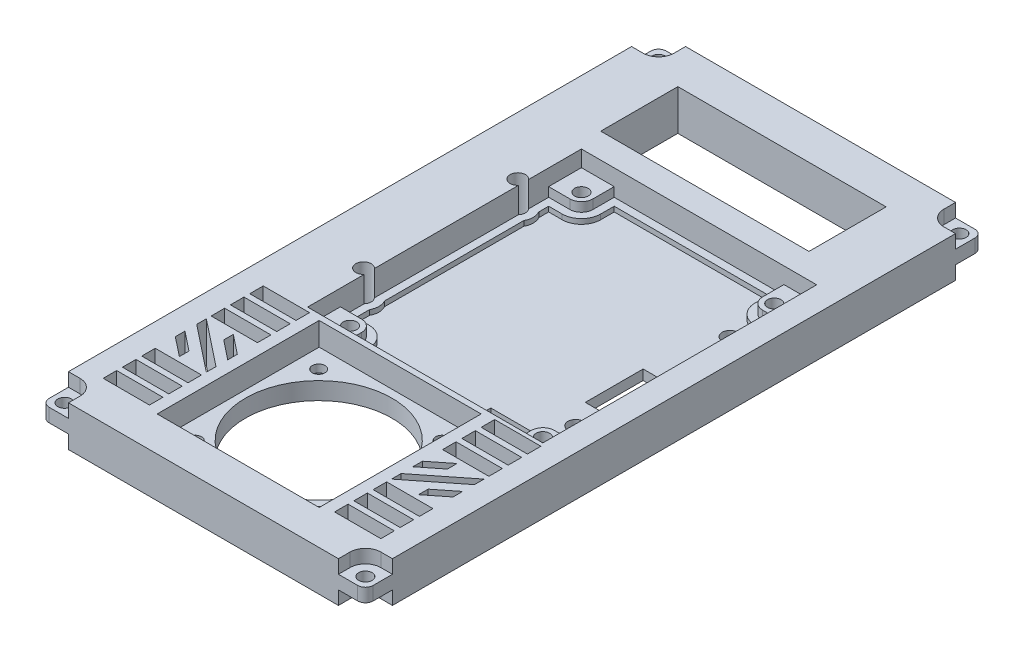
SolidWorks part; units mm, degrees
ref_plane "前视基准面" through (0, 0, 0) normal (0, 0, 1) x (1, 0, 0)
ref_plane "上视基准面" through (0, 0, 0) normal (0, 1, 0) x (1, 0, 0)
ref_plane "右视基准面" through (0, 0, 0) normal (1, 0, 0) x (0, 0, -1)
sketch "草图1" plane through (0, 0, 0) normal (0, 1, 0) x (1, 0, 0)
  line L1 (0, 0) -> (84, 0)
  line L2 (0, 0) -> (0, 160)
  line L3 (0, 160) -> (84, 160)
  line L4 (84, 0) -> (84, 160)
  dimension "D1" = 84
  dimension "D2" = 160
extrude "凸台-拉伸1" add sketch "草图1" along normal blind 10.5
fillet "圆角1" radius 2 4 edges at (0, 5.25, 0) (0, 5.25, -160) (84, 5.25, -160) (84, 5.25, 0)
sketch "草图2" plane through (0, 10.5, 0) normal (0, 1, 0) x (1, 0, 0)
  line L0 (0, 158) -> (0, 2) construction
  line L1 (2, 0) -> (82, 0) construction
  line L2 (42, 160) -> (42, 0) construction
  line L3 (82, 160) -> (2, 160) construction
  line L20 (73, 27.25) -> (78, 31.2083)
  line L21 (73, 24.75) -> (73, 27.25)
  line L22 (78, 28.7083) -> (73, 24.75)
  line L23 (78, 31.2083) -> (78, 28.7083)
  line L36 (66, 24.75) -> (66, 27.25)
  line L38 (6, 28.7083) -> (11, 24.75)
  line L40 (78, 34.25) -> (66, 24.75)
  line L42 (6, 36.75) -> (18, 36.75) construction
  line L43 (6, 36.75) -> (6, 24.75) construction
  line L44 (6, 24.75) -> (18, 24.75) construction
  line L45 (18, 36.75) -> (18, 24.75) construction
  line L46 (6, 36.75) -> (18, 24.75) construction
  line L47 (6, 24.75) -> (18, 36.75) construction
  line L48 (11, 24.75) -> (11, 27.25)
  line L49 (11, 27.25) -> (6, 31.2083)
  line L50 (6, 31.2083) -> (6, 28.7083)
  line L55 (6, 36.75) -> (6, 34.25)
  line L56 (6, 34.25) -> (18, 24.75)
  line L57 (18, 24.75) -> (18, 27.25)
  line L58 (18, 27.25) -> (6, 36.75)
  line L59 (13, 36.75) -> (13, 34.25)
  line L60 (13, 34.25) -> (18, 30.2917)
  line L61 (18, 30.2917) -> (18, 32.7917)
  line L62 (18, 32.7917) -> (13, 36.75)
  line L63 (78, 36.75) -> (78, 34.25)
  line L64 (66, 27.25) -> (78, 36.75)
  line L65 (66, 30.2917) -> (66, 32.7917)
  line L66 (71, 34.25) -> (66, 30.2917)
  line L67 (71, 36.75) -> (71, 34.25)
  line L68 (66, 32.7917) -> (71, 36.75)
  line L69 (6, 41.5) -> (6, 38)
  line L70 (6, 13.5) -> (18, 13.5)
  line L71 (6, 13.5) -> (6, 10)
  line L72 (6, 10) -> (18, 10)
  line L73 (18, 13.5) -> (18, 10)
  line L74 (6, 41.5) -> (18, 41.5)
  line L75 (18, 41.5) -> (18, 38)
  line L76 (6, 38) -> (18, 38)
  line L77 (6, 18.5) -> (6, 15)
  line L78 (6, 18.5) -> (18, 18.5)
  line L79 (18, 18.5) -> (18, 15)
  line L80 (6, 15) -> (18, 15)
  line L81 (6, 46.5) -> (6, 43)
  line L82 (6, 43) -> (18, 43)
  line L83 (18, 46.5) -> (18, 43)
  line L84 (6, 46.5) -> (18, 46.5)
  line L85 (6, 23.5) -> (6, 20)
  line L86 (6, 23.5) -> (18, 23.5)
  line L87 (18, 23.5) -> (18, 20)
  line L88 (6, 20) -> (18, 20)
  line L89 (6, 51.5) -> (6, 48)
  line L90 (6, 48) -> (18, 48)
  line L91 (18, 51.5) -> (18, 48)
  line L92 (6, 51.5) -> (18, 51.5)
  line L93 (78, 10) -> (66, 10)
  line L94 (66, 13.5) -> (66, 10)
  line L95 (78, 13.5) -> (66, 13.5)
  line L96 (78, 13.5) -> (78, 10)
  line L97 (78, 18.5) -> (66, 18.5)
  line L98 (66, 18.5) -> (66, 15)
  line L99 (78, 15) -> (66, 15)
  line L100 (78, 18.5) -> (78, 15)
  line L101 (78, 23.5) -> (66, 23.5)
  line L102 (66, 23.5) -> (66, 20)
  line L103 (78, 20) -> (66, 20)
  line L104 (78, 23.5) -> (78, 20)
  line L105 (78, 41.5) -> (66, 41.5)
  line L106 (66, 41.5) -> (66, 38)
  line L107 (78, 38) -> (66, 38)
  line L108 (78, 41.5) -> (78, 38)
  line L109 (78, 46.5) -> (66, 46.5)
  line L110 (66, 46.5) -> (66, 43)
  line L111 (78, 43) -> (66, 43)
  line L112 (78, 46.5) -> (78, 43)
  line L113 (78, 51.5) -> (66, 51.5)
  line L114 (66, 51.5) -> (66, 48)
  line L115 (78, 48) -> (66, 48)
  line L116 (78, 51.5) -> (78, 48)
  point P33 (12, 30.75)
  dimension "D1" = 6
  dimension "D4" = 24.75
  dimension "D5" = 6
  dimension "D6" = 10
  dimension "D7" = 3.5
  dimension "D8" = 12
  dimension "D9" = 2
  dimension "D10" = 3
  dimension "D25" = 12
  dimension "D26" = 12
  dimension "D27" = 2.5
  dimension "D28" = 2.5
  dimension "D29" = 2.5
  dimension "D30" = 5
  dimension "D31" = 5
extrude "切除-拉伸1" cut sketch "草图2" against normal through all
sketch "草图4" plane through (0, 10.5, 0) normal (0, 1, 0) x (1, 0, 0)
  line L0 (-0.1195, 30) -> (83.8805, 30) construction
  line L3 (41.8805, 0) -> (41.8805, 72.0189) construction
  line L5 (2, 0) -> (82, 0) construction
  line L6 (25.8805, 46) -> (57.8805, 46) construction
  line L7 (25.8805, 46) -> (25.8805, 14) construction
  line L8 (25.8805, 14) -> (57.8805, 14) construction
  line L9 (57.8805, 46) -> (57.8805, 14) construction
  circle A0 centre (41.8805, 30) radius 19
  circle A1 centre (57.8805, 14) radius 1.65
  circle A2 centre (57.8805, 46) radius 1.65
  circle A3 centre (25.8805, 46) radius 1.65
  circle A4 centre (25.8805, 14) radius 1.65
  dimension "D1" = 38
  dimension "D7" = 3.3
  dimension "D2" = 30
  dimension "D3" = 32
  dimension "D4" = 32
  dimension "D5" = 16
  dimension "D6" = 16
extrude "切除-拉伸2" cut sketch "草图4" against normal through all
sketch "草图6" plane through (0, 10.5, 0) normal (0, 1, 0) x (1, 0, 0)
  line L1 (82, 160) -> (2, 160) construction
  line L13 (66, 90) -> (76, 90)
  line L14 (66, 90) -> (66, 75)
  line L15 (66, 75) -> (76, 75)
  line L16 (76, 90) -> (76, 75)
  line L35 (55, 55) -> (67.5, 55)
  line L36 (55, 55) -> (55, 61.5)
  line L37 (55, 61.5) -> (67.5, 61.5)
  line L38 (67.5, 55) -> (67.5, 61.5)
  line L40 (84, 2) -> (84, 158) construction
  line L41 (2, 0) -> (82, 0) construction
  dimension "D2" = 70
  dimension "D3" = 8
  dimension "D4" = 16.5
  dimension "D5" = 55
  dimension "D6" = 12.5
  dimension "D7" = 6.5
  dimension "D8" = 10
  dimension "D10" = 15
extrude "切除-拉伸3" cut sketch "草图6" against normal through all
sketch "草图7" plane through (0, 10.5, 0) normal (0, 1, 0) x (1, 0, 0)
  line L0 (0, 108.5) -> (84, 108.5) construction
  line L3 (0, 68.5) -> (84, 68.5) construction
  line L4 (15, 108.5) -> (15, 68.5) construction
  line L5 (70, 108.5) -> (70, 68.5) construction
  line L7 (0, 158) -> (0, 2) construction
  line L8 (82, 160) -> (2, 160) construction
  circle A0 centre (15, 108.5) radius 2
  circle A1 centre (70, 108.5) radius 2
  circle A2 centre (15, 68.5) radius 2
  circle A3 centre (70, 68.5) radius 2
  dimension "D1" = 4
  dimension "D2" = 15
  dimension "D3" = 40
  dimension "D4" = 51.5
  dimension "D5" = 55
extrude "切除-拉伸4" cut sketch "草图7" against normal through all
sketch "草图8" plane through (0, 10.5, 0) normal (0, 1, 0) x (1, 0, 0)
  line L0 (42, 160) -> (42, 166.0083)
  line L1 (82, 160) -> (2, 160) construction
  line L4 (55, 55) -> (67.5, 55)
  line L5 (67.5, 55) -> (67.5, 61.5)
  line L6 (67.5, 61.5) -> (55, 61.5)
  line L7 (55, 61.5) -> (55, 55)
  line L25 (84, 160) -> (0, 160) construction
  line L28 (0, 160) -> (0, 0) construction
  line L31 (0, 0) -> (84, 0) construction
  line L34 (84, 0) -> (84, 160) construction
  line L176 (42, 30) -> (61, 30) construction
  line L177 (42, 30) -> (42, 11) construction
  line L179 (21, 51) -> (63, 51)
  line L180 (21, 51) -> (21, 9)
  line L181 (21, 9) -> (63, 9)
  line L182 (63, 51) -> (63, 9)
  line L189 (16.5, 123.5) -> (77.5, 123.5)
  line L190 (16.5, 123.5) -> (16.5, 52.5)
  line L191 (16.5, 52.5) -> (77.5, 52.5)
  line L192 (77.5, 123.5) -> (77.5, 52.5)
  line L194 (22, 118) -> (72, 118) construction
  line L195 (22, 118) -> (22, 58) construction
  line L196 (22, 58) -> (72, 58) construction
  line L197 (72, 118) -> (72, 58) construction
  circle A0 centre (22, 58) radius 1.75
  circle A1 centre (72, 58) radius 1.75
  circle A4 centre (72, 118) radius 1.75
  circle A5 centre (22, 118) radius 1.75
  circle A6 centre (81, 157) radius 1.75
  circle A7 centre (3, 157) radius 1.75
  circle A13 centre (22, 58) radius 3
  circle A14 centre (22, 118) radius 3
  circle A15 centre (72, 118) radius 3
  circle A16 centre (72, 58) radius 3
  circle A19 centre (81, 3) radius 1.75
  circle A20 centre (3, 3) radius 1.75
  dimension "D15" = 6
  dimension "D7" = 3.5
  dimension "D2" = 42
  dimension "D3" = 42
  dimension "D4" = 21
  dimension "D5" = 21
  dimension "D6" = 6.5
  dimension "D8" = 61
  dimension "D9" = 71
  dimension "D10" = 52.5
  dimension "D11" = 60
  dimension "D12" = 50
  dimension "D13" = 5.5
  dimension "D14" = 5.5
extrude "切除-拉伸5" cut sketch "草图8" against normal through all contours A7 | A6 | A4 | A5 | A0 | A1 | A19 | A20 region at (22, 10.5, -58) region at (72, 10.5, -58) region at (72, 10.5, -118) region at (22, 10.5, -118) region at (81, 10.5, -157) region at (3, 10.5, -157) region at (81, 10.5, -3) region at (3, 10.5, -3)
sketch "草图9" plane through (0, 10.5, 0) normal (0, 1, 0) x (1, 0, 0)
  line L8 (7, 160) -> (2, 160)
  line L9 (0, 158) -> (0, 153)
  line L10 (0, 153) -> (3, 153)
  line L11 (7, 157) -> (7, 160)
  line L16 (84, 153) -> (84, 158)
  line L17 (82, 160) -> (77, 160)
  line L18 (77, 160) -> (77, 157)
  line L19 (81, 153) -> (84, 153)
  line L24 (0, 7) -> (0, 2)
  line L25 (2, 0) -> (7, 0)
  line L26 (7, 0) -> (7, 3)
  line L27 (3, 7) -> (0, 7)
  line L32 (77, 0) -> (82, 0)
  line L33 (84, 2) -> (84, 7)
  line L34 (84, 7) -> (81, 7)
  line L35 (77, 3) -> (77, 0)
  arc A4 (2, 160) -> (0, 158) centre (2, 158) ccw
  arc A5 (3, 153) -> (7, 157) centre (3, 157) ccw
  arc A8 (84, 158) -> (82, 160) centre (82, 158) ccw
  arc A9 (77, 157) -> (81, 153) centre (81, 157) ccw
  arc A12 (0, 2) -> (2, 0) centre (2, 2) ccw
  arc A13 (7, 3) -> (3, 7) centre (3, 3) ccw
  arc A16 (82, 0) -> (84, 2) centre (82, 2) ccw
  arc A17 (81, 7) -> (77, 3) centre (81, 3) ccw
extrude "切除-拉伸6" cut sketch "草图9" against normal blind 3.5
extrude "切除-拉伸8" cut sketch "草图9<2>" along normal blind 3.5 from surface starting at face at (81, 0, -155.25)
sketch "草图9<2>" plane through (0, 10.5, 0) normal (0, 1, 0) x (1, 0, 0) same geometry as "草图9"
sketch "草图10" plane through (0, 0, 0) normal (0, -1, 0) x (-1, 0, 0)
  circle A0 centre (-71.8805, 118) radius 3.5
  circle A1 centre (-21.8805, 118) radius 3.5
  circle A2 centre (-21.8805, 58) radius 3.5
  circle A3 centre (-71.8805, 58) radius 3.5
  circle A8 centre (-57.8805, 14) radius 3
  circle A9 centre (-25.8805, 14) radius 3
  circle A10 centre (-25.8805, 46) radius 3
  circle A11 centre (-57.8805, 46) radius 3
  dimension "D1" = 7
extrude "切除-拉伸7" cut sketch "草图10" against normal blind 2.5
extrude "切除-拉伸9" cut sketch "草图8<4>" against normal blind 6 contours L182 L179 L180 L181 region at (42, 10.5, -30)
sketch "草图8<4>" plane through (0, 10.5, 0) normal (0, 1, 0) x (1, 0, 0) same geometry as "草图8"
extrude "切除-拉伸10" cut sketch "草图8<5>" against normal blind 6.5 contours L189 L192 L191 L190
sketch "草图8<5>" plane through (0, 10.5, 0) normal (0, 1, 0) x (1, 0, 0) same geometry as "草图8"
extrude "凸台-拉伸2" add sketch "草图8<6>" along normal blind 2.3 from surface contours A14 A5 | A15 A4 | A16 A1 | A13 A0 region at (19.0849, 10.5, -58) region at (19.0849, 10.5, -118) region at (69.0849, 10.5, -118) region at (69.0849, 10.5, -58) starting at face at (71, 4, -82.5)
sketch "草图8<6>" plane through (0, 10.5, 0) normal (0, 1, 0) x (1, 0, 0) same geometry as "草图8"
sketch "草图11" plane through (0, 4, 0) normal (0, 1, 0) x (1, 0, 0)
  line L0 (22, 115) -> (16.5, 115)
  line L1 (16.5, 123.5) -> (16.5, 109.8229) construction
  line L2 (16.5, 115) -> (16.5, 123.5)
  line L3 (16.5, 123.5) -> (25, 123.5)
  line L4 (16.5, 123.5) -> (77.5, 123.5) construction
  line L5 (25, 123.5) -> (25, 118)
  line L6 (72, 115) -> (77.5, 115)
  line L7 (77.5, 123.5) -> (77.5, 52.5) construction
  line L8 (77.5, 115) -> (77.5, 123.5)
  line L9 (77.5, 123.5) -> (69, 123.5)
  line L10 (16.5, 123.5) -> (77.5, 123.5) construction
  line L11 (69, 123.5) -> (69, 118)
  line L12 (72, 61) -> (77.5, 61)
  line L13 (77.5, 123.5) -> (77.5, 52.5) construction
  line L14 (77.5, 61) -> (77.5, 52.5)
  line L15 (77.5, 52.5) -> (69, 52.5)
  line L16 (16.5, 52.5) -> (77.5, 52.5) construction
  line L17 (69, 52.5) -> (69, 58)
  line L18 (22, 61) -> (16.5, 61)
  line L19 (16.5, 67.1771) -> (16.5, 52.5) construction
  line L20 (16.5, 61) -> (16.5, 52.5)
  line L21 (16.5, 52.5) -> (25, 52.5)
  line L22 (16.5, 52.5) -> (77.5, 52.5) construction
  line L23 (25, 52.5) -> (25, 58)
  circle A0 centre (22, 118) radius 3 construction
  circle A1 centre (22, 118) radius 3 construction
  circle A2 centre (72, 118) radius 3 construction
  circle A3 centre (72, 118) radius 3 construction
  circle A4 centre (72, 58) radius 3 construction
  circle A5 centre (72, 58) radius 3 construction
  circle A6 centre (22, 58) radius 3 construction
  circle A7 centre (22, 58) radius 3 construction
  circle A8 centre (22, 58) radius 3
  circle A9 centre (72, 58) radius 3
  circle A10 centre (72, 118) radius 3
  circle A11 centre (22, 118) radius 3
  circle M1 centre (72, 58) radius 3
  circle M2 centre (22, 118) radius 3
  line M12 (16.5, 67.1771) -> (16.5, 52.5)
  line M13 (16.5, 52.5) -> (77.5, 52.5)
  line M14 (77.5, 52.5) -> (77.5, 123.5)
  line M15 (77.5, 123.5) -> (16.5, 123.5)
  line M16 (16.5, 123.5) -> (16.5, 109.8229)
  circle M21 centre (72, 118) radius 3
  circle M22 centre (22, 58) radius 3
extrude "凸台-拉伸3" add sketch "草图11" along normal blind 2.3 contours L5 L0 M15 M16 M2 | L11 L6 M15 M21 M14 | L17 L12 M13 M14 M1 | L23 L18 M13 M22 M12 region at (19.7449, 4, -55.7449) region at (74.2551, 4, -55.7449) region at (74.2551, 4, -120.2551) region at (19.7449, 4, -120.2551)
sketch "草图12" plane through (0, 4, 0) normal (0, 1, 0) x (1, 0, 0)
  line L14 (25, 58) -> (25, 52.5)
  line L15 (25, 52.5) -> (69, 52.5)
  line L16 (69, 52.5) -> (69, 58)
  line L17 (72, 61) -> (77.5, 61)
  line L18 (77.5, 61) -> (77.5, 115)
  line L19 (77.5, 115) -> (72, 115)
  line L20 (69, 118) -> (69, 123.5)
  line L21 (69, 123.5) -> (25, 123.5)
  line L22 (25, 123.5) -> (25, 118)
  line L23 (22, 115) -> (16.5, 115)
  line L24 (16.5, 115) -> (16.5, 109.8229)
  line L25 (16.5, 107.1771) -> (16.5, 69.8229)
  line L26 (16.5, 67.1771) -> (16.5, 61)
  line L27 (16.5, 61) -> (22, 61)
  line L28 (25, 58) -> (25, 52.5)
  line L29 (25, 52.5) -> (69, 52.5)
  line L30 (69, 52.5) -> (69, 58)
  line L31 (72, 61) -> (77.5, 61)
  line L32 (77.5, 61) -> (77.5, 115)
  line L33 (77.5, 115) -> (72, 115)
  line L34 (69, 118) -> (69, 123.5)
  line L35 (69, 123.5) -> (25, 123.5)
  line L36 (25, 123.5) -> (25, 118)
  line L37 (22, 115) -> (16.5, 115)
  line L38 (16.5, 115) -> (16.5, 109.8229)
  line L39 (16.5, 107.1771) -> (16.5, 69.8229)
  line L40 (16.5, 67.1771) -> (16.5, 61)
  line L41 (16.5, 61) -> (22, 61)
  arc A6 (25, 58) -> (22, 61) centre (22, 58) ccw
  arc A8 (25, 58) -> (22, 61) centre (22, 58) ccw
  arc A10 (16.5, 107.1771) -> (16.5, 109.8229) centre (15, 108.5) ccw
  arc A11 (16.5, 67.1771) -> (16.5, 69.8229) centre (15, 68.5) ccw
  arc A16 (16.5, 107.1771) -> (16.5, 109.8229) centre (15, 108.5) ccw
  arc A17 (16.5, 67.1771) -> (16.5, 69.8229) centre (15, 68.5) ccw
  arc A18 (72, 61) -> (69, 58) centre (72, 58) ccw
  arc A20 (72, 61) -> (69, 58) centre (72, 58) ccw
  arc A22 (69, 118) -> (72, 115) centre (72, 118) ccw
  arc A23 (69, 118) -> (72, 115) centre (72, 118) ccw
  arc A24 (22, 115) -> (25, 118) centre (22, 118) ccw
  arc A25 (22, 115) -> (25, 118) centre (22, 118) ccw
  dimension "D1" = 0
extrude "切除-拉伸-薄壁1" cut sketch "草图12" against normal blind 0.1 thin thin type one direction reverse wall 2
sketch "草图13" plane through (0, 4, 0) normal (0, 1, 0) x (1, 0, 0)
  line L22 (72, 63) -> (75.5, 63)
  line L23 (75.5, 63) -> (75.5, 75)
  line L24 (75.5, 75) -> (66, 75)
  line L25 (66, 75) -> (66, 90)
  line L26 (66, 90) -> (75.5, 90)
  line L27 (75.5, 90) -> (75.5, 113)
  line L28 (75.5, 113) -> (72, 113)
  line L29 (67, 118) -> (67, 121.5)
  line L30 (67, 121.5) -> (27, 121.5)
  line L31 (27, 121.5) -> (27, 118)
  line L32 (22, 113) -> (18.5, 113)
  line L33 (18.5, 113) -> (18.5, 110.4365)
  line L34 (18.5, 106.5635) -> (18.5, 70.4365)
  line L35 (18.5, 66.5635) -> (18.5, 63)
  line L36 (18.5, 63) -> (22, 63)
  line L37 (27, 58) -> (27, 54.5)
  line L38 (27, 54.5) -> (67, 54.5)
  line L39 (67, 54.5) -> (67, 55)
  line L40 (67, 55) -> (55, 55)
  line L41 (55, 55) -> (55, 61.5)
  line L42 (55, 61.5) -> (67.5, 61.5)
  line L43 (67.5, 61.5) -> (67.5, 60.1794)
  line L44 (72, 63) -> (75.5, 63)
  line L45 (75.5, 63) -> (75.5, 75)
  line L46 (75.5, 75) -> (66, 75)
  line L47 (66, 75) -> (66, 90)
  line L48 (66, 90) -> (75.5, 90)
  line L49 (75.5, 90) -> (75.5, 113)
  line L50 (75.5, 113) -> (72, 113)
  line L51 (67, 118) -> (67, 121.5)
  line L52 (67, 121.5) -> (27, 121.5)
  line L53 (27, 121.5) -> (27, 118)
  line L54 (22, 113) -> (18.5, 113)
  line L55 (18.5, 113) -> (18.5, 110.4365)
  line L56 (18.5, 106.5635) -> (18.5, 70.4365)
  line L57 (18.5, 66.5635) -> (18.5, 63)
  line L58 (18.5, 63) -> (22, 63)
  line L59 (27, 58) -> (27, 54.5)
  line L60 (27, 54.5) -> (67, 54.5)
  line L61 (67, 54.5) -> (67, 55)
  line L62 (67, 55) -> (55, 55)
  line L63 (55, 55) -> (55, 61.5)
  line L64 (55, 61.5) -> (67.5, 61.5)
  line L65 (67.5, 61.5) -> (67.5, 60.1794)
  arc A6 (67, 118) -> (72, 113) centre (72, 118) ccw
  arc A8 (18.5, 106.5635) -> (18.5, 110.4365) centre (15, 108.5) ccw
  arc A9 (18.5, 66.5635) -> (18.5, 70.4365) centre (15, 68.5) ccw
  arc A10 (67, 118) -> (72, 113) centre (72, 118) ccw
  arc A14 (18.5, 106.5635) -> (18.5, 110.4365) centre (15, 108.5) ccw
  arc A15 (18.5, 66.5635) -> (18.5, 70.4365) centre (15, 68.5) ccw
  arc A18 (22, 113) -> (27, 118) centre (22, 118) ccw
  arc A20 (22, 113) -> (27, 118) centre (22, 118) ccw
  arc A22 (27, 58) -> (22, 63) centre (22, 58) ccw
  arc A23 (27, 58) -> (22, 63) centre (22, 58) ccw
  arc A24 (72, 63) -> (67.5, 60.1794) centre (72, 58) ccw
  arc A25 (72, 63) -> (67.5, 60.1794) centre (72, 58) ccw
  dimension "D1" = 0
extrude "切除-拉伸11" cut sketch "草图13" against normal blind 1.4
sketch "草图14" plane through (0, 10.5, 0) normal (0, 1, 0) x (1, 0, 0)
  line L0 (0, 153) -> (0, 7) construction
  line L1 (15, 150) -> (69, 150)
  line L2 (15, 150) -> (15, 130)
  line L3 (15, 130) -> (69, 130)
  line L4 (69, 150) -> (69, 130)
  line L5 (84, 7) -> (84, 153) construction
  line L6 (77, 160) -> (7, 160) construction
  dimension "D1" = 15
  dimension "D2" = 15
  dimension "D3" = 10
  dimension "D4" = 20
extrude "切除-拉伸12" cut sketch "草图14" against normal through all
